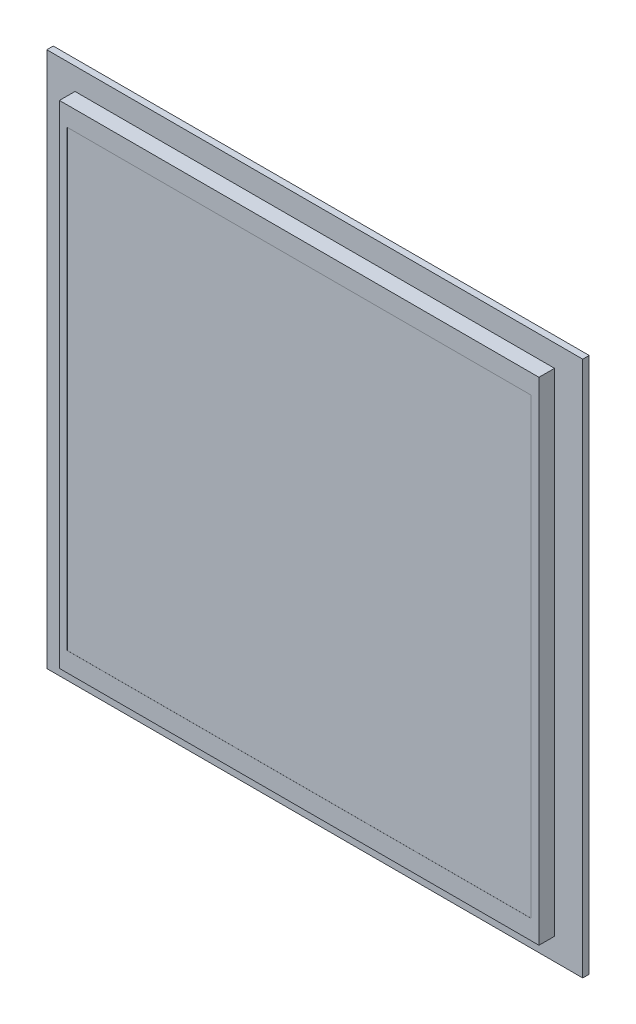
SolidWorks part; units mm, degrees
ref_plane "Спереди" through (0, 0, 0) normal (0, 0, 1) x (1, 0, 0)
ref_plane "Сверху" through (0, 0, 0) normal (0, 1, 0) x (1, 0, 0)
ref_plane "Справа" through (0, 0, 0) normal (1, 0, 0) x (0, 0, -1)
sketch "Эскиз1" plane through (0, 0, 0) normal (0, 0, 1) x (1, 0, 0)
  line L8 (-35.928, -35.088) -> (-35.928, 35.088)
  line L13 (-37.13, 0) -> (37.13, 0)
  line L14 (0, -38.09) -> (0, 38.09)
  line L15 (-37.13, 38.09) -> (37.13, 38.09)
  line L16 (37.13, -38.09) -> (37.13, 38.09)
  line L21 (-41.5, 0) -> (41.5, 0)
  line L22 (0, -41.5) -> (0, 41.5)
  line L23 (-41.5, 41.5) -> (41.5, 41.5)
  line L24 (41.5, -41.5) -> (41.5, 41.5)
  line L25 (-35.928, 0) -> (35.928, 0)
  line L26 (0, -35.088) -> (0, 35.088)
  line L27 (-35.928, 35.088) -> (35.928, 35.088)
  line L28 (35.928, -35.088) -> (35.928, 35.088)
  line L29 (-41.5, -41.5) -> (-41.5, 41.5)
  line L30 (-37.13, -38.09) -> (-37.13, 38.09)
  line L31 (-35.928, -35.088) -> (35.928, -35.088)
  line L32 (-41.5, -41.5) -> (41.5, -41.5)
  line L33 (-37.13, -38.09) -> (37.13, -38.09)
  point P26 (0, 0)
  dimension "D1" = 37.13
  dimension "D2" = 41.5
  dimension "D4" = 38.09
  dimension "D3" = 41.5
  dimension "D5" = 35.928
  dimension "D6" = 35.088
extrude "Бобышка-Вытянуть2" add sketch "Эскиз1" along normal blind 1 contours L28 L21 L16 L15 L22 L27 | L21 L30 L15 L22 L23 L29 | L30 L13 L8 L27 L22 L15 | L21 L24 L23 L22 L15 L16 | L13 L28 L27 L14 | L27 L8 L13 L14 | L8 L31 L22 L13 | L22 L31 L28 L13 | L33 L22 L32 L24 L21 L16 | L14 L33 L16 L21 L28 L31 | L30 L33 L14 L31 L8 L13 | L33 L30 L21 L29 L32 L22 region at (-17.964, -35.6199, 0) region at (-17.964, -17.544, 0) region at (-36.529, 0.5319, 0) region at (-17.964, 17.544, 0) region at (17.964, -35.6199, 0) region at (17.964, -17.544, 0) region at (-37.7169, -19.045, 0) region at (-39.315, 0.5869, 0) region at (17.964, 17.544, 0) region at (18.565, -38.6769, 0) region at (0.5319, 36.589, 0) region at (0.5869, 39.795, 0)
extrude "Бобышка-Вытянуть5" add sketch "Эскиз1<5>" along normal blind 3.4 contours L27 L28 L31 L8
sketch "Эскиз1<5>" plane through (0, 0, 0) normal (0, 0, 1) x (1, 0, 0) same geometry as "Эскиз1"
extrude "Бобышка-Вытянуть6" add sketch "Эскиз1<6>" along normal blind 3.41 contours L30 L13 L8 L27 L22 L15 | L28 L21 L16 L15 L22 L27 | L14 L33 L16 L21 L28 L31 | L30 L33 L14 L31 L8 L13 region at (-17.964, -35.6199, 0) region at (-36.529, 0.5319, 0) region at (17.964, -35.6199, 0) region at (0.5319, 36.589, 0)
sketch "Эскиз1<6>" plane through (0, 0, 0) normal (0, 0, 1) x (1, 0, 0) same geometry as "Эскиз1"
